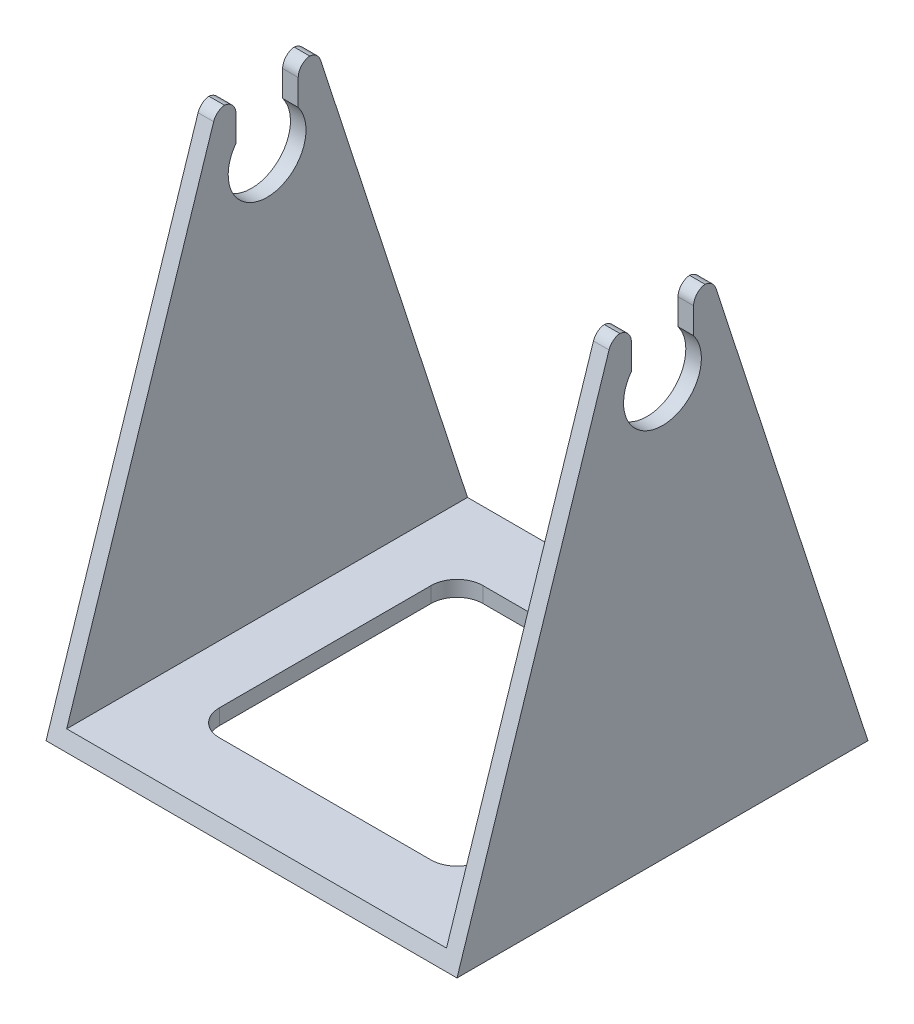
SolidWorks part; units mm, degrees
ref_plane "Front Plane" through (0, 0, 0) normal (0, 0, 1) x (1, 0, 0)
ref_plane "Top Plane" through (0, 0, 0) normal (0, 1, 0) x (1, 0, 0)
ref_plane "Right Plane" through (0, 0, 0) normal (1, 0, 0) x (0, 0, -1)
sketch "Sketch1" plane through (0, 0, 0) normal (0, 1, 0) x (1, 0, 0)
  line L1 (-39.6, 39.6) -> (39.6, 39.6)
  line L2 (-39.6, 39.6) -> (-39.6, -39.6)
  line L3 (-39.6, -39.6) -> (39.6, -39.6)
  line L4 (39.6, 39.6) -> (39.6, -39.6)
  line L5 (-39.6, 39.6) -> (39.6, -39.6) construction
  line L6 (-39.6, -39.6) -> (39.6, 39.6) construction
  point P0 (0, 0)
  dimension "D1" = 79.2
  dimension "D2" = 79.2
extrude "Boss-Extrude1" add sketch "Sketch1" along normal blind 3
sketch "Sketch2" plane through (0, 3, 0) normal (0, 1, 0) x (1, 0, 0)
  line L1 (-20.4, -25.4) -> (20.4, -25.4)
  line L2 (-25.4, -20.4) -> (-25.4, 20.4)
  line L3 (-20.4, 25.4) -> (20.4, 25.4)
  line L4 (25.4, -20.4) -> (25.4, 20.4)
  line L5 (-25.4, -25.4) -> (25.4, 25.4) construction
  line L6 (-25.4, 25.4) -> (25.4, -25.4) construction
  arc A0 (20.4, -25.4) -> (25.4, -20.4) centre (20.4, -20.4) ccw
  arc A1 (-20.4, -25.4) -> (-25.4, -20.4) centre (-20.4, -20.4) cw
  arc A2 (20.4, 25.4) -> (25.4, 20.4) centre (20.4, 20.4) cw
  arc A3 (-25.4, 20.4) -> (-20.4, 25.4) centre (-20.4, 20.4) cw
  point P0 (0, 0)
  dimension "D3" = 5
  dimension "D1" = 50.8
  dimension "D2" = 50.8
extrude "Cut-Extrude1" cut sketch "Sketch2" against normal blind 3
sketch "Sketch3" plane through (0, 3, 0) normal (0, 1, 0) x (1, 0, 0)
  line L0 (-39.6, -39.6) -> (39.6, -39.6) construction
  line L1 (-39.6, 39.6) -> (-36.6, 39.6)
  line L2 (-39.6, 39.6) -> (-39.6, -39.6)
  line L3 (-39.6, -39.6) -> (-36.6, -39.6)
  line L4 (-36.6, 39.6) -> (-36.6, -39.6)
  line L6 (39.6, 39.6) -> (36.6, 39.6)
  line L7 (39.6, 39.6) -> (39.6, -39.6)
  line L8 (39.6, -39.6) -> (36.6, -39.6)
  line L9 (36.6, 39.6) -> (36.6, -39.6)
  dimension "D1" = 3
  dimension "D2" = 3
extrude "Boss-Extrude2" add sketch "Sketch3" along normal blind 88.9
sketch "Sketch4" plane through (39.6, 0, 0) normal (1, 0, 0) x (0, 0, -1)
  line L0 (-39.6, 0) -> (-9.7399, 91.9)
  line L1 (-39.6, 91.9) -> (39.6, 91.9) construction
  line L2 (-9.7399, 91.9) -> (-41.7099, 102.2877)
  line L3 (-41.7099, 102.2877) -> (-62.7263, 13.3368)
  line L4 (-62.7263, 13.3368) -> (-39.6, 0)
  line L5 (39.6, 0) -> (9.7399, 91.9)
  line L6 (9.7399, 91.9) -> (57.35, 101.5648)
  line L7 (57.35, 101.5648) -> (39.6, 0)
  line L8 (-39.6, 0) -> (39.6, 0) construction
  dimension "D1" = 72
  dimension "D2" = 72
extrude "Cut-Extrude2" cut sketch "Sketch4" against normal blind 88.9
sketch "Sketch5" plane through (39.6, 0, 0) normal (1, 0, 0) x (0, 0, -1)
  line L0 (-9.7399, 91.9) -> (9.7399, 91.9) construction
  circle A0 centre (0, 79.9) radius 7.5
  dimension "D1" = 15
  dimension "D2" = 12
extrude "Cut-Extrude3" cut sketch "Sketch5" against normal blind 88.9
sketch "Sketch6" plane through (-39.6, 0, 0) normal (-1, 0, 0) x (0, 0, 1)
  line L1 (-6, 94.9) -> (6, 94.9)
  line L2 (-6, 94.9) -> (-6, 79.9)
  line L3 (-6, 79.9) -> (6, 79.9)
  line L4 (6, 94.9) -> (6, 79.9)
  line L5 (-6, 94.9) -> (6, 79.9) construction
  line L6 (-6, 79.9) -> (6, 94.9) construction
  circle A0 centre (0, 79.9) radius 7.5 construction
  point P0 (0, 87.4)
  dimension "D1" = 12
extrude "Cut-Extrude4" cut sketch "Sketch6" against normal blind 88.9
fillet "Fillet1" radius 2.5 8 edges at (38.1, 91.9, 6) (38.1, 91.9, 9.7399) (38.1, 91.9, -6) (38.1, 91.9, -9.7399) (-38.1, 91.9, 6) (-38.1, 91.9, -6) (-38.1, 91.9, -9.7399) (-38.1, 91.9, 9.7399)
